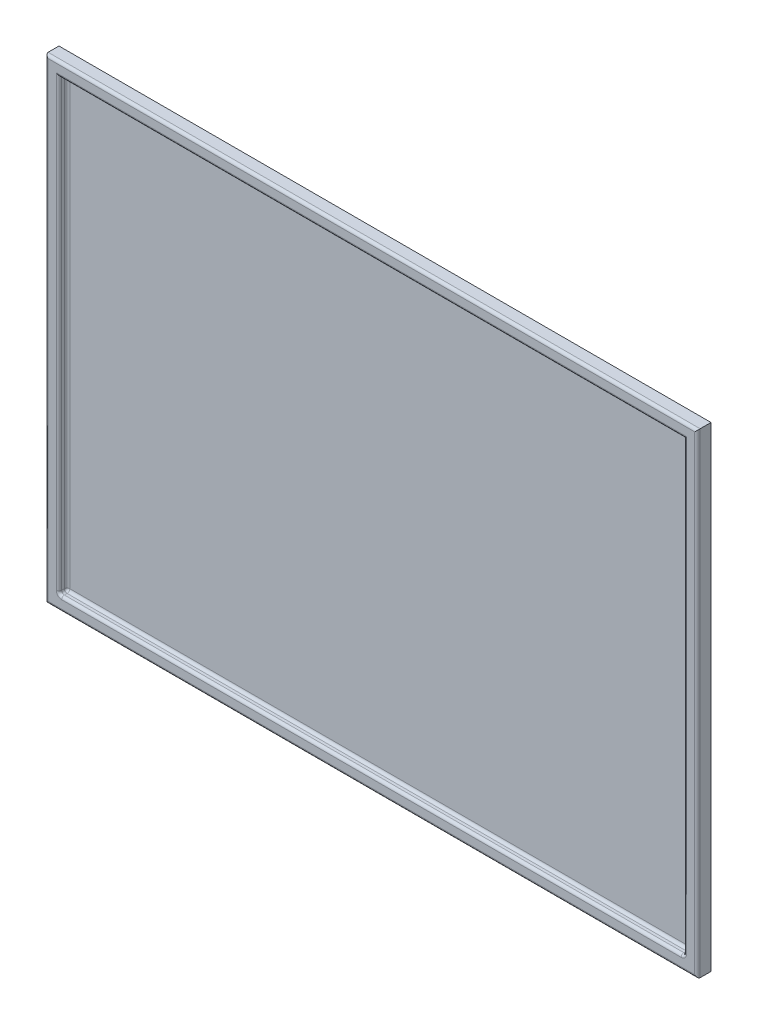
SolidWorks part; units mm, degrees
ref_plane "Front Plane" through (0, 0, 0) normal (0, 0, 1) x (1, 0, 0)
ref_plane "Top Plane" through (0, 0, 0) normal (0, 1, 0) x (1, 0, 0)
ref_plane "Right Plane" through (0, 0, 0) normal (1, 0, 0) x (0, 0, -1)
sketch "Sketch1" plane through (0, 0, 0) normal (0, 0, 1) x (1, 0, 0)
  line L1 (-115.1823, 67.813) -> (124.8177, 67.813)
  line L2 (-115.1823, 67.813) -> (-115.1823, -107.187)
  line L3 (-115.1823, -107.187) -> (124.8177, -107.187)
  line L4 (124.8177, 67.813) -> (124.8177, -107.187)
  dimension "D1" = 240
  dimension "D2" = 175
extrude "Boss-Extrude1" add sketch "Sketch1" along normal blind 5
sketch "Sketch2" plane through (0, 0, 5) normal (0, 0, 1) x (1, 0, 0)
  line L8 (-110.1823, 62.813) -> (-110.1823, -102.187)
  line L9 (-110.1823, -102.187) -> (119.8177, -102.187)
  line L10 (119.8177, -102.187) -> (119.8177, 62.813)
  line L11 (119.8177, 62.813) -> (-110.1823, 62.813)
  line L12 (-110.1823, 62.813) -> (-110.1823, -102.187)
  line L13 (-110.1823, -102.187) -> (119.8177, -102.187)
  line L14 (119.8177, -102.187) -> (119.8177, 62.813)
  line L15 (119.8177, 62.813) -> (-110.1823, 62.813)
  dimension "D1" = 5
extrude "Cut-Extrude1" cut sketch "Sketch2" against normal blind 3
fillet "Fillet1" radius 1 7 edges at (-110.1823, -102.187, 3.5) (4.8177, -102.187, 2) (119.8177, -102.187, 3.5) (4.8177, -102.187, 5) (-110.1823, -19.687, 5) (4.8177, 62.813, 5) (119.8177, -19.687, 5)
fillet "Fillet2" radius 1 4 edges at (4.8177, -107.187, 5) (124.8177, -19.687, 5) (4.8177, 67.813, 5) (-115.1823, -19.687, 5)
fillet "Fillet3" radius 1 5 edges at (119.5249, -101.8941, 2.2929) (-109.8894, -101.8941, 2.2929) (119.8177, -19.187, 2) (4.8177, 62.813, 2) (-110.1823, -19.187, 2)
